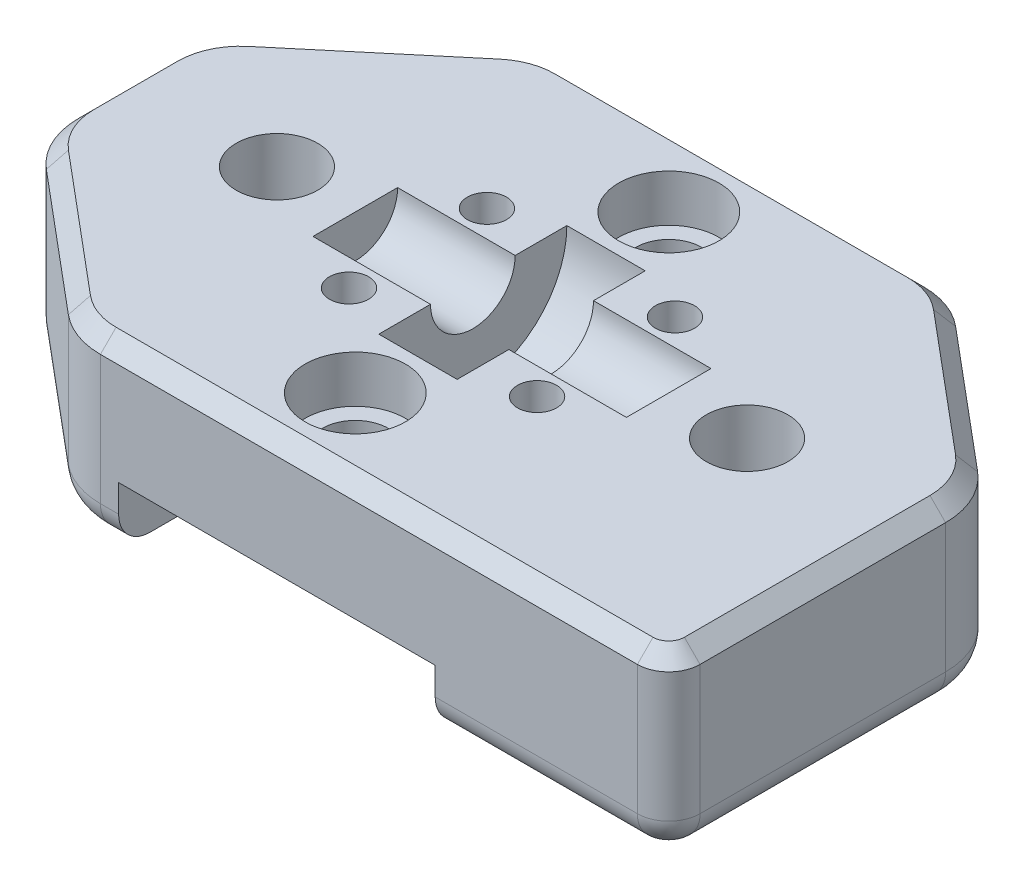
SolidWorks part; units mm, degrees
ref_plane "Front Plane" through (0, 0, 0) normal (0, 0, 1) x (1, 0, 0)
ref_plane "Top Plane" through (0, 0, 0) normal (0, 1, 0) x (1, 0, 0)
ref_plane "Right Plane" through (0, 0, 0) normal (1, 0, 0) x (0, 0, -1)
sketch "Sketch1" plane through (0, 0, 0) normal (0, 1, 0) x (1, 0, 0)
  line L0 (14.3035, 0) -> (-14.3035, 0)
  line L1 (-18.3852, 1.4856) -> (-29.4817, 10.7967)
  line L2 (-31.75, 15.6611) -> (-31.75, 22.4389)
  line L3 (-31.75, 19.05) -> (0, 19.05) construction
  line L4 (0, 19.05) -> (0, 0) construction
  line L6 (31.75, 15.6611) -> (31.75, 22.4389)
  line L7 (-18.3852, 36.6144) -> (-29.4817, 27.3033)
  line L8 (14.3035, 38.1) -> (-14.3035, 38.1)
  line L9 (18.3852, 36.6144) -> (29.4817, 27.3033)
  line L10 (14.3035, 0) -> (29.21, 0)
  line L11 (31.75, 2.54) -> (31.75, 15.6611)
  arc A0 (-29.4817, 10.7967) -> (-31.75, 15.6611) centre (-25.4, 15.6611) cw
  arc A1 (-18.3852, 1.4856) -> (-14.3035, 0) centre (-14.3035, 6.35) ccw
  arc A4 (-29.4817, 27.3033) -> (-31.75, 22.4389) centre (-25.4, 22.4389) ccw
  arc A5 (-18.3852, 36.6144) -> (-14.3035, 38.1) centre (-14.3035, 31.75) cw
  arc A6 (18.3852, 36.6144) -> (14.3035, 38.1) centre (14.3035, 31.75) ccw
  arc A7 (29.4817, 27.3033) -> (31.75, 22.4389) centre (25.4, 22.4389) cw
  arc A8 (31.75, 2.54) -> (29.21, 0) centre (29.21, 2.54) cw
  point P9 (-31.75, 12.7)
  point P31 (31.75, 19.05)
  dimension "D5" = 6.35
  dimension "D6" = 6.35
  dimension "D7" = 2.54
  dimension "D1" = 19.05
  dimension "D2" = 6.35
  dimension "D3" = 31.75
  dimension "D4" = 140
extrude "Boss-Extrude2" add sketch "Sketch1" along normal blind 14.2875
sketch "Sketch2" plane through (0, 14.2875, 0) normal (0, 1, 0) x (1, 0, 0)
  line L0 (-14.3035, 0) -> (29.21, 0) construction
  line L2 (14.3035, 38.1) -> (-14.3035, 38.1) construction
  line L3 (0, 38.1) -> (0, 0) construction
  circle A0 centre (-19.05, 19.05) radius 3.302
  circle A3 centre (19.05, 19.05) radius 3.302
  circle A8 centre (7.62, 24.638) radius 1.5875
  circle A9 centre (7.62, 13.462) radius 1.5875
  circle A10 centre (-7.62, 13.462) radius 1.5875
  circle A11 centre (-7.62, 24.638) radius 1.5875
  circle A12 centre (0, 31.75) radius 2.667
  circle A13 centre (0, 6.35) radius 2.667
  dimension "D2" = 6.604
  dimension "D7" = 7.62
  dimension "D8" = 3.175
  dimension "D10" = 5.588
  dimension "D4" = 5.334
  dimension "D3" = 19.05
  dimension "D5" = 6.35
  dimension "D6" = 6.35
  dimension "D9" = 5.588
  dimension "D11" = 7.62
  dimension "D12" = 25.4
  dimension "D13" = 19.05
extrude "Cut-Extrude1" cut sketch "Sketch2" against normal through all
sketch "Sketch3" plane through (-31.75, 0, 0) normal (-1, 0, 0) x (0, 0, 1)
  line L0 (-22.4389, 14.2875) -> (-15.6611, 14.2875) construction
  circle A0 centre (-19.05, 14.2875) radius 3.429
  dimension "D1" = 6.858
extrude "Cut-Extrude3" cut sketch "Sketch3" against normal blind 25.4 from offset 19.05 offset against normal yes
sketch "Sketch4" plane through (-31.75, 0, 0) normal (-1, 0, 0) x (0, 0, 1)
  line L0 (-22.4389, 14.2875) -> (-15.6611, 14.2875) construction
  line L1 (-26.67, 14.2875) -> (-11.43, 14.2875)
  arc A0 (-26.67, 14.2875) -> (-11.43, 14.2875) centre (-19.05, 14.2875) ccw
  dimension "D1" = 7.62
extrude "Cut-Extrude4" cut sketch "Sketch4" against normal blind 6.35 from offset 28.575 offset against normal yes
sketch "Sketch5" plane through (0, 0, -38.1) normal (0, 0, -1) x (-1, 0, 0)
  line L0 (-14.3035, 0) -> (14.3035, 0) construction
  line L1 (12.827, 0) -> (-12.827, 0)
  line L2 (12.827, 0) -> (12.827, 4.7625)
  line L3 (12.827, 4.7625) -> (-12.827, 4.7625)
  line L4 (-12.827, 0) -> (-12.827, 4.7625)
  line L5 (-14.3035, 14.2875) -> (14.3035, 14.2875) construction
  point P10 (0, 14.2875)
  dimension "D1" = 25.654
  dimension "D2" = 4.7625
  dimension "D3" = 12.827
extrude "Cut-Extrude5" cut sketch "Sketch5" against normal through all
sketch "Sketch6" plane through (0, 0, 0) normal (0, -1, 0) x (1, 0, 0)
  line L1 (13.208, -22.4229) -> (19.05, -25.7958)
  line L2 (19.05, -25.7958) -> (24.892, -22.4229)
  line L3 (24.892, -22.4229) -> (24.892, -15.6771)
  line L4 (24.892, -15.6771) -> (19.05, -12.3042)
  line L5 (19.05, -12.3042) -> (13.208, -15.6771)
  line L6 (13.208, -15.6771) -> (13.208, -22.4229)
  line L7 (-19.05, -25.7958) -> (-13.208, -22.4229)
  line L8 (-13.208, -22.4229) -> (-13.208, -15.6771)
  line L9 (-13.208, -15.6771) -> (-19.05, -12.3042)
  line L10 (-19.05, -12.3042) -> (-24.892, -15.6771)
  line L11 (-24.892, -15.6771) -> (-24.892, -22.4229)
  line L12 (-24.892, -22.4229) -> (-19.05, -25.7958)
  circle A0 centre (19.05, -19.05) radius 5.842 construction
  circle A1 centre (-19.05, -19.05) radius 5.842 construction
  dimension "D1" = 11.684
extrude "Cut-Extrude6" cut sketch "Sketch6" against normal blind 6.35
sketch "Sketch9" plane through (0, 4.7625, 0) normal (0, -1, 0) x (1, 0, 0)
  line L0 (9.2075, -13.462) -> (9.2075, -24.638)
  line L1 (6.0325, -13.462) -> (6.0325, -24.638)
  line L2 (-6.0325, -24.638) -> (-6.0325, -13.462)
  line L3 (-9.2075, -24.638) -> (-9.2075, -13.462)
  circle A0 centre (7.62, -13.462) radius 1.5875 construction
  circle A1 centre (7.62, -24.638) radius 1.5875 construction
  circle A2 centre (-7.62, -24.638) radius 1.5875 construction
  circle A3 centre (-7.62, -13.462) radius 1.5875 construction
  arc A4 (9.2075, -24.638) -> (6.0325, -24.638) centre (7.62, -24.638) cw
  arc A5 (-6.0325, -24.638) -> (-9.2075, -24.638) centre (-7.62, -24.638) cw
  arc A6 (-9.2075, -13.462) -> (-6.0325, -13.462) centre (-7.62, -13.462) cw
  arc A7 (6.0325, -13.462) -> (9.2075, -13.462) centre (7.62, -13.462) cw
extrude "Cut-Extrude9" cut sketch "Sketch9" against normal blind 3.175
chamfer "Chamfer2" distance 2.54 angle 45 4 edges at (-7.62, 7.9375, -15.0495) (-7.62, 7.9375, -23.0505) (7.62, 7.9375, -15.0495) (7.62, 7.9375, -23.0505)
sketch "Sketch10" plane through (0, 14.2875, 0) normal (0, 1, 0) x (1, 0, 0)
  circle A0 centre (0, 6.35) radius 4.064
  circle A1 centre (0, 31.7584) radius 4.064
  dimension "D1" = 8.128
extrude "Cut-Extrude10" cut sketch "Sketch10" against normal blind 3.81
fillet "Fillet1" radius 2.54 16 edges at (-31.1551, 0, -25.1226) (-31.75, 0, -19.05) (-31.1551, 0, -12.9774) (-23.9335, 0, -6.1411) (-16.4753, 0, -0.383) (-13.5653, 0, 0) (-23.9335, 0, -31.9589) (-16.4753, 0, -37.717) (-13.5653, 0, -38.1) (21.0185, 0, 0) (31.75, 0, -12.4895) (31.1551, 0, -25.1226) (23.9335, 0, -31.9589) (16.4753, 0, -37.717) (13.5653, 0, -38.1) (31.0061, 0, -0.7439)
fillet "Fillet2" radius 1.27 8 edges at (-7.62, 4.7625, -26.2255) (-9.2075, 4.7625, -19.05) (-7.62, 4.7625, -11.8745) (-6.0325, 4.7625, -19.05) (7.62, 4.7625, -11.8745) (9.2075, 4.7625, -19.05) (7.62, 4.7625, -26.2255) (6.0325, 4.7625, -19.05)
chamfer "Chamfer3" distance 1.27 angle 45 14 edges at (16.4753, 14.2875, -37.717) (0, 14.2875, -38.1) (-16.4753, 14.2875, -37.717) (-23.9335, 14.2875, -31.9589) (-31.1551, 14.2875, -25.1226) (-31.75, 14.2875, -19.05) (-31.1551, 14.2875, -12.9774) (-23.9335, 14.2875, -6.1411) (-16.4753, 14.2875, -0.383) (7.4532, 14.2875, 0) (31.75, 14.2875, -12.4895) (31.1551, 14.2875, -25.1226) (23.9335, 14.2875, -31.9589) (31.0061, 14.2875, -0.7439)
